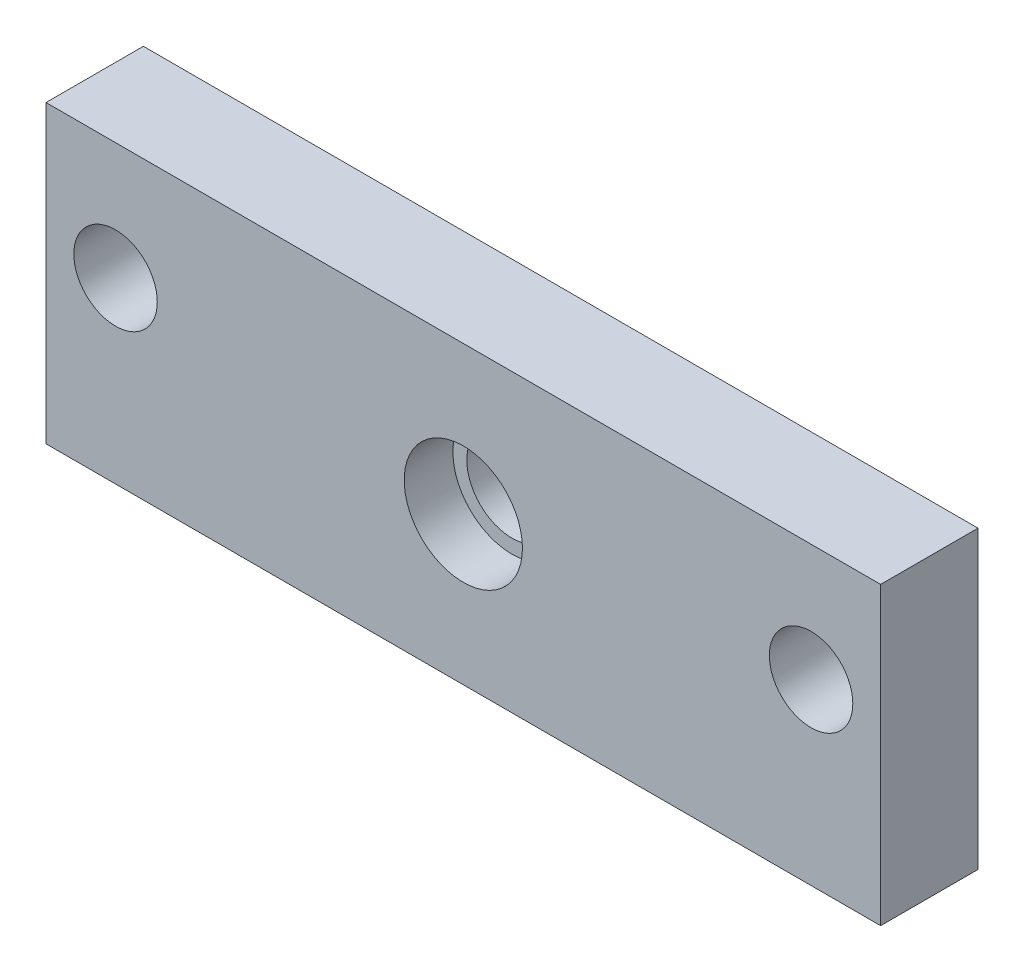
SolidWorks part; units mm, degrees
ref_plane "Front Plane" through (0, 0, 0) normal (0, 0, 1) x (1, 0, 0)
ref_plane "Top Plane" through (0, 0, 0) normal (0, 1, 0) x (1, 0, 0)
ref_plane "Right Plane" through (0, 0, 0) normal (1, 0, 0) x (0, 0, -1)
sketch "Sketch1" plane through (0, 0, 0) normal (0, 0, 1) x (1, 0, 0)
  line L1 (-60, -21.25) -> (60, -21.25)
  line L2 (-60, -21.25) -> (-60, 21.25)
  line L3 (-60, 21.25) -> (60, 21.25)
  line L4 (60, -21.25) -> (60, 21.25)
  line L5 (-60, -21.25) -> (60, 21.25) construction
  line L6 (-60, 21.25) -> (60, -21.25) construction
  point P0 (0, 0)
  dimension "D1" = 120
  dimension "D2" = 42.5
extrude "Boss-Extrude1" add sketch "Sketch1" along normal mid plane 14
sketch "Sketch2" plane through (0, 0, 7) normal (0, 0, 1) x (1, 0, 0)
  circle A0 centre (0, 0) radius 8.5
  dimension "D1" = 17
extrude "Cut-Extrude1" cut sketch "Sketch2" against normal blind 7
sketch "Sketch3" plane through (0, 0, 0) normal (0, 0, 1) x (1, 0, 0)
  circle A0 centre (0, 0) radius 6.5
  dimension "D1" = 13
extrude "Cut-Extrude2" cut sketch "Sketch3" against normal through all
sketch "Sketch5" plane through (0, 0, 7) normal (0, 0, 1) x (1, 0, 0)
  line L0 (-40.6477, 4.4) -> (36.4799, 4.4) construction
  circle A0 centre (-50, 4.4) radius 6
  circle A1 centre (50, 4.4) radius 6
  dimension "D1" = 12
  dimension "D2" = 12
  dimension "D4" = 50
  dimension "D3" = 50
  dimension "D5" = 4.4
extrude "Cut-Extrude4" cut sketch "Sketch5" against normal through all
sketch "Sketch6" plane through (0, -21.25, 0) normal (0, -1, 0) x (1, 0, 0)
  line L0 (-60, 0) -> (60, 0) construction
  line L1 (-60, 7) -> (-60, -7) construction
  line L2 (60, 7) -> (60, -7) construction
  circle A0 centre (-50, 0) radius 2.5
  circle A1 centre (-25, 0) radius 2.5
  circle A2 centre (25, 0) radius 2.5
  circle A3 centre (50, 0) radius 2.5
  circle A4 centre (-37.5, 0) radius 1.25
  circle A5 centre (37.5, 0) radius 1.25
  dimension "D1" = 5
  dimension "D2" = 5
  dimension "D3" = 5
  dimension "D4" = 5
  dimension "D5" = 10
  dimension "D9" = 2.5
  dimension "D10" = 2.5
  dimension "D11" = 22.5
  dimension "D12" = 22.5
  dimension "D6" = 35
  dimension "D7" = 10
  dimension "D8" = 35
extrude "Cut-Extrude5" cut sketch "Sketch6" against normal blind 10
